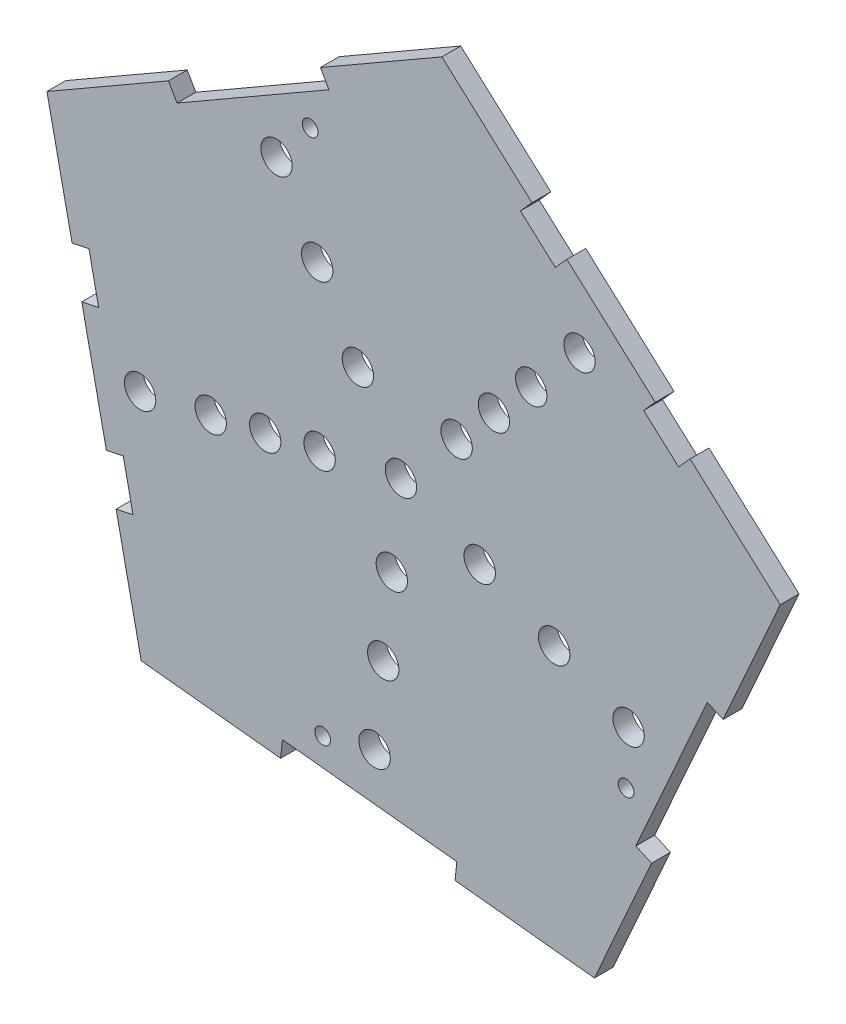
SolidWorks part; units mm, degrees
ref_plane "Front Plane" through (0, 0, 0) normal (0, 0, 1) x (1, 0, 0)
ref_plane "Top Plane" through (0, 0, 0) normal (0, 1, 0) x (1, 0, 0)
ref_plane "Right Plane" through (0, 0, 0) normal (1, 0, 0) x (0, 0, -1)
sketch "Sketch1" plane through (0, 0, 0) normal (0, 0, 1) x (1, 0, 0)
  line L1 (-82.808, -91.7686) -> (61.688, -107.1132)
  line L2 (61.688, -107.1132) -> (120.9333, 25.569)
  line L3 (120.9333, 25.569) -> (13.0529, 122.9157)
  line L4 (13.0529, 122.9157) -> (-112.8662, 50.3971)
  line L5 (-112.8662, 50.3971) -> (-82.808, -91.7686)
  circle A0 centre (0, 0) radius 100 construction
extrude "Boss-Extrude1" add sketch "Sketch1" along normal blind 6 contours L4 L5 L1 L2 L3
sketch "Sketch2" plane through (0, 0, 6) normal (0, 0, 1) x (1, 0, 0)
  line L0 (3.3497, 3.7121) -> (0, 0) construction
  line L2 (4.5655, -2.0386) -> (0, 0) construction
  line L5 (-2.4953, 4.3328) -> (0, 0) construction
  line L7 (0, 0) -> (-4.8919, -1.0343) construction
  line L8 (0, 0) -> (-0.528, -4.972) construction
  circle A6 centre (0, 0) radius 5
extrude "Cut-Extrude1" cut sketch "Sketch2" against normal blind 6 contours A6
sketch "Sketch8" plane through (0, 0, 6) normal (0, 0, 1) x (1, 0, 0)
  line L4 (-82.808, -91.7686) -> (61.688, -107.1132) construction
  line L5 (16.0987, -27.9532) -> (31.5598, 6.6727)
  line L6 (31.5598, 6.6727) -> (3.4064, 32.0772)
  line L8 (3.4064, 32.0772) -> (-29.4546, 13.1521)
  line L9 (-29.4546, 13.1521) -> (-21.6103, -23.9488)
  line L10 (-21.6103, -23.9488) -> (16.0987, -27.9532)
  line L11 (-21.6103, -23.9488) -> (-29.4145, -97.4386)
  line L12 (16.0987, -27.9532) -> (8.2945, -101.4431)
  line L13 (16.0987, -27.9532) -> (83.5801, -58.085)
  line L14 (61.688, -107.1132) -> (120.9333, 25.569) construction
  line L15 (31.5598, 6.6727) -> (99.0413, -23.4591)
  line L16 (31.5598, 6.6727) -> (81.0698, 61.5401)
  line L17 (120.9333, 25.569) -> (13.0529, 122.9157) construction
  line L18 (3.4064, 32.0772) -> (52.9164, 86.9446)
  line L19 (3.4064, 32.0772) -> (-33.4762, 96.1189)
  line L20 (13.0529, 122.9157) -> (-112.8662, 50.3971) construction
  line L21 (-29.4546, 13.1521) -> (-66.3371, 77.1938)
  line L22 (13.0529, 122.9157) -> (-112.8662, 50.3971) construction
  line L23 (-29.4546, 13.1521) -> (-101.7592, -2.1354)
  line L24 (-112.8662, 50.3971) -> (-82.808, -91.7686) construction
  line L25 (-21.6103, -23.9488) -> (-93.915, -39.2362)
  line L26 (16.0987, -27.9532) -> (12.4292, -36.1712) construction
  line L27 (31.5598, 6.6727) -> (35.2293, 14.8907) construction
  line L28 (12.4292, -36.1712) -> (79.9106, -66.303)
  line L29 (35.2293, 14.8907) -> (102.7107, -15.2411)
  circle A0 centre (0, 0) radius 32.2575 construction
  dimension "D1" = 9
  dimension "D2" = 9
sketch "Sketch11" plane through (0, 0, 6) normal (0, 0, 1) x (1, 0, 0)
  line L0 (-8.976, -84.5247) -> (-6.5472, -61.6533) construction
  line L1 (-21.6103, -23.9488) -> (-29.4145, -97.4386) construction
  line L2 (-6.5472, -61.6533) -> (-4.6728, -44.0026) construction
  line L3 (-4.6728, -44.0026) -> (-2.7984, -26.3518) construction
  line L4 (8.2945, -101.4431) -> (8.8753, -95.9738)
  line L5 (8.2945, -101.4431) -> (23.2106, -103.0271)
  line L6 (8.8753, -95.9738) -> (23.7914, -97.5578)
  line L7 (23.2106, -103.0271) -> (23.7914, -97.5578)
  line L8 (-29.4145, -97.4386) -> (-28.8337, -91.9694)
  line L9 (-28.8337, -91.9694) -> (-43.7498, -90.3854)
  line L10 (-44.3306, -95.8546) -> (-43.7498, -90.3854)
  line L11 (-29.4145, -97.4386) -> (-44.3306, -95.8546)
  line L12 (-82.808, -91.7686) -> (61.688, -107.1132) construction
  circle A0 centre (0, 0) radius 62
  circle A1 centre (-6.5472, -61.6533) radius 5
  circle A2 centre (0, 0) radius 44.25
  circle A3 centre (-4.6728, -44.0026) radius 5
  circle A4 centre (0, 0) radius 26.5
  circle A5 centre (-2.7984, -26.3518) radius 5
  circle A6 centre (-8.976, -84.5247) radius 5
  dimension "D2" = 17.75
  dimension "D3" = 17.75
  dimension "D1" = 23
extrude "Cut-Extrude2" cut sketch "Sketch11" against normal blind 10 contours A2 A3 | A2 A3 | A4 A5 | A4 A5 | A1 | A6 region at (-4.4434, -41.8426, 6) region at (-4.8914, -46.0614, 6) region at (-2.5656, -24.1594, 6) region at (-3.0133, -28.3753, 6)
sketch "Sketch12" plane through (0, 0, 6) normal (0, 0, 1) x (1, 0, 0)
  line L0 (72.592, -32.4138) -> (48.8512, -21.8131) construction
  line L1 (16.0987, -27.9532) -> (83.5801, -58.085) construction
  line L2 (48.8512, -21.8131) -> (25.1104, -11.2123) construction
  line L3 (31.5598, 6.6727) -> (99.0413, -23.4591) construction
  circle A0 centre (0, 0) radius 53.5
  circle A1 centre (48.8512, -21.8131) radius 5
  circle A2 centre (0, 0) radius 27.5
  circle A3 centre (25.1104, -11.2123) radius 5
  circle A5 centre (84.8224, -20.3523) radius 2.5
  circle A6 centre (72.592, -32.4138) radius 5
  dimension "D2" = 26
  dimension "D1" = 26
extrude "Cut-Extrude3" cut sketch "Sketch12" against normal blind 10 contours A2 A3 | A6 | A1 | A3 | A5 region at (26.9714, -12.0433, 6) region at (72.592, -32.4138, 6)
extrude "Cut-Extrude4" cut sketch "Sketch11<3>" against normal blind 10 contours L6 L7 L5 L4 | L11 L10 L9 L8
sketch "Sketch11<3>" plane through (0, 0, 6) normal (0, 0, 1) x (1, 0, 0) same geometry as "Sketch11"
ref_plane "Plane4" through (0, 0, 0) normal (-0.4077, -0.9131, 0) x (-0.9131, 0.4077, 0)
ref_plane "Plane5" through (0, 0, 0) normal (0.7424, -0.6699, 0) x (0, 0, -1)
mirror "Mirror3" about plane through (0, 0, 0) normal (-0.4077, -0.9131, 0) of "Cut-Extrude2"
mirror "Mirror4" about plane through (0, 0, 0) normal (0.7424, -0.6699, 0) of "Cut-Extrude3"
mirror "Mirror5" about plane through (0, 0, 0) normal (0.7424, -0.6699, 0) of "Cut-Extrude2"
mirror "Mirror6" about plane through (0, 0, 0) normal (-0.4077, -0.9131, 0) of "Cut-Extrude4"
mirror "Mirror7" about plane through (0, 0, 0) normal (0.7424, -0.6699, 0) of "Cut-Extrude4"
sketch "Sketch13" plane through (0, 0, 6) normal (0, 0, 1) x (1, 0, 0)
  line L0 (79.9106, -66.303) -> (102.7107, -15.2411)
  line L1 (79.9106, -66.303) -> (74.8885, -64.0605)
  line L2 (102.7107, -15.2411) -> (97.6887, -12.9987)
  line L3 (74.8885, -64.0605) -> (97.6887, -12.9987)
extrude "Cut-Extrude5" cut sketch "Sketch13" against normal blind 10 contours L3 L2 L0 L1
mirror "Mirror8" about plane through (0, 0, 0) normal (0.7424, -0.6699, 0) of "Cut-Extrude5"
sketch "Sketch14" plane through (0, 0, 0) normal (0, 0, -1) x (-1, 0, 0)
  line L0 (-3.0133, -1.3455) -> (3.0133, 1.3455) construction
  circle A0 centre (-84.8224, -20.3523) radius 2.5
  circle A1 centre (-71.7754, -49.5718) radius 2.5
extrude "Boss-Extrude2" add sketch "Sketch14" against normal blind 6 contours A0 region at (84.8224, -20.3523, 0)
extrude "Cut-Extrude6" cut sketch "Sketch14<3>" against normal blind 6 contours A1
sketch "Sketch14<3>" plane through (0, 0, 0) normal (0, 0, -1) x (-1, 0, 0) same geometry as "Sketch14"
extrude "Boss-Extrude3" add sketch "Sketch11<4>" against normal blind 6 contours A6 | A0 A1 | A0 A1 | A4 A5 | A4 A5 | A3 | L5 L7 L6 L4 | L9 L10 L11 L8 region at (-6.3193, -59.5074, 6) region at (-6.7674, -63.727, 6) region at (-2.5656, -24.1594, 6) region at (-3.0133, -28.3753, 6) region at (-8.976, -84.5247, 6)
sketch "Sketch11<4>" plane through (0, 0, 6) normal (0, 0, 1) x (1, 0, 0) same geometry as "Sketch11"
ref_plane "Plane6" through (0, 0, 0) normal (0.8666, 0.4991, 0) x (0, 0, -1)
mirror "Mirror9" about plane through (0, 0, 0) normal (0.8666, 0.4991, 0) of "Cut-Extrude5", "Cut-Extrude3"
